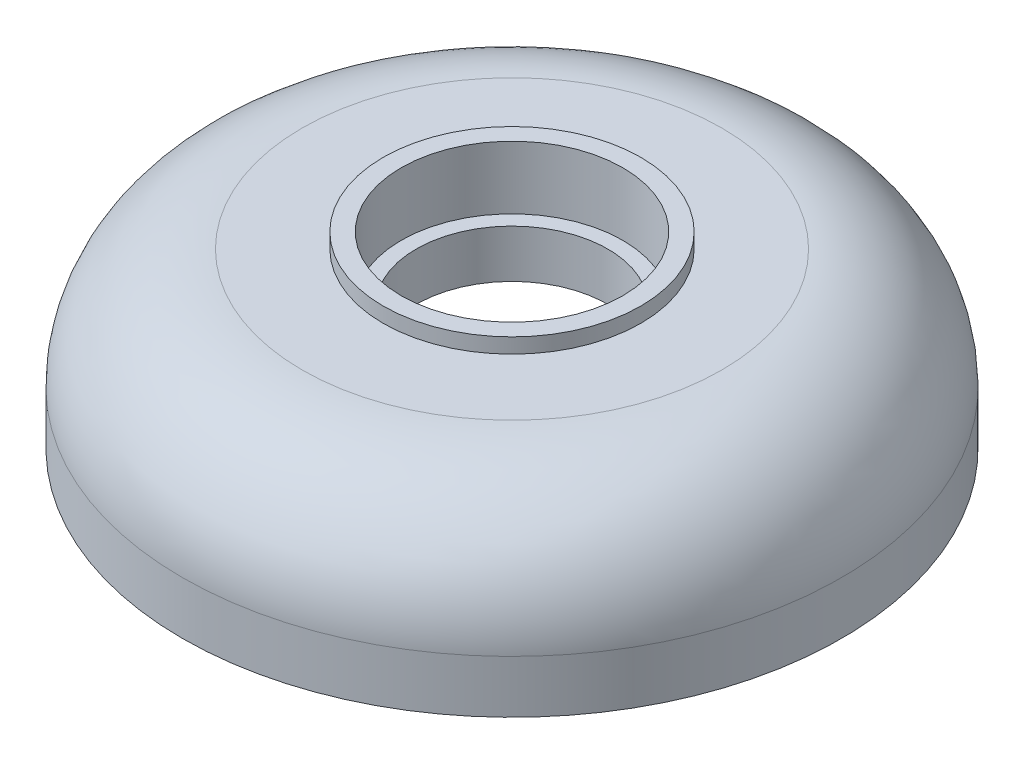
SolidWorks part; units mm, degrees
ref_plane "Front Plane" through (0, 0, 0) normal (0, 0, 1) x (1, 0, 0)
ref_plane "Top Plane" through (0, 0, 0) normal (0, 1, 0) x (1, 0, 0)
ref_plane "Right Plane" through (0, 0, 0) normal (1, 0, 0) x (0, 0, -1)
sketch "Sketch1" plane through (0, 0, 0) normal (0, 0, 1) x (1, 0, 0)
  line L10 (-55, 10.2042) -> (-45, 10.2042)
  line L11 (-45, 10.2042) -> (-45, 13.691)
  line L12 (-40.8682, 18.6151) -> (-16, 23)
  line L13 (-16, 23) -> (-16, 31)
  line L14 (-16, 31) -> (-18.5, 31)
  line L15 (-18.5, 31) -> (-18.5, 41.5)
  line L16 (-21.5, 39) -> (-35, 39)
  line L17 (-55, 19) -> (-55, 10.2042)
  line L23 (0, 95.7864) -> (0, -110.3116) construction
  line L25 (-18.5, 41.5) -> (-21.5, 41.5)
  line L26 (-21.5, 41.5) -> (-21.5, 39)
  arc A0 (-35, 39) -> (-55, 19) centre (-35, 19) ccw
  arc A1 (-45, 13.691) -> (-40.8682, 18.6151) centre (-40, 13.691) cw
  point P2 (0, 0)
  point P4 (-18.5, 41.668)
  point P7 (0, 0)
  point P14 (9.3787, 15.0941)
  point P15 (-27.7077, 6.7569)
  point P16 (0, 0)
  point P19 (-45, 17.8865)
  dimension "D1" = 20
  dimension "D10" = 5
  dimension "D2" = 32
  dimension "D3" = 100
  dimension "D4" = 8
  dimension "D5" = 16
  dimension "D6" = 110
  dimension "D7" = 3
  dimension "D8" = 2.5
  dimension "D9" = 17.8865
revolve "Revolve1" add sketch "Sketch1" angle 360 about L23
